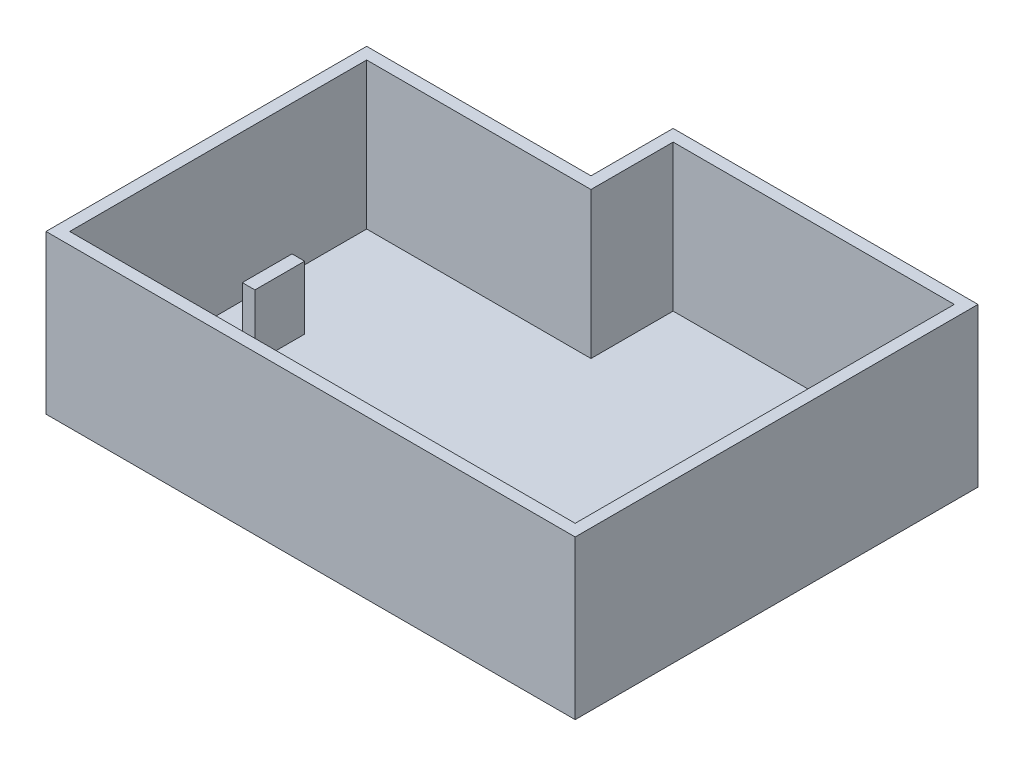
SolidWorks part; units mm, degrees
material "Cedro"
ref_plane "Alzado" through (0, 0, 0) normal (0, 0, 1) x (1, 0, 0)
ref_plane "Planta" through (0, 0, 0) normal (0, 1, 0) x (1, 0, 0)
ref_plane "Vista lateral" through (0, 0, 0) normal (1, 0, 0) x (0, 0, -1)
sketch "Croquis1" plane through (0, 0, 0) normal (0, 1, 0) x (1, 0, 0)
  line L0 (-106.3625, -93.6625) -> (-106.3625, 93.6625)
  line L1 (-101.6, -88.9) -> (101.6, -88.9)
  line L2 (-101.6, -88.9) -> (-101.6, 88.9)
  line L3 (-101.6, 88.9) -> (101.6, 88.9)
  line L4 (101.6, -88.9) -> (101.6, 88.9)
  line L5 (-101.6, -88.9) -> (101.6, 88.9) construction
  line L6 (-101.6, 88.9) -> (101.6, -88.9) construction
  line L7 (-106.3625, 93.6625) -> (106.3625, 93.6625)
  line L8 (106.3625, -93.6625) -> (106.3625, 93.6625)
  line L9 (-106.3625, -93.6625) -> (106.3625, -93.6625)
  point P0 (0, 0)
  dimension "D1" = 203.2
  dimension "D2" = 177.8
  dimension "D3" = 4.7625
extrude "Saliente-Extruir1" add sketch "Croquis1" along normal blind 63.608 contours L1 L4 L3 L2 | L0 L9 L8 L7 L4 L1 L2 L3 region at (-103.528, 0, 0) region at (0, 0, 0)
shell "Vaciado1" thickness 4.7625 removed face at (0, 63.608, 0)
sketch "Croquis2" plane through (0, 4.7625, 0) normal (0, 1, 0) x (1, 0, 0)
  line L0 (-77.47, 10) -> (-77.47, -10)
  line L1 (-101.6, 88.9) -> (101.6, 88.9) construction
  line L3 (10, -64.77) -> (-10, -64.77)
  line L4 (-54.45, 58.42) -> (-34.45, 58.42)
  line L5 (-101.6, -88.9) -> (-101.6, 88.9) construction
  line L6 (-101.6, -88.9) -> (101.6, -88.9) construction
  line L7 (101.6, -88.9) -> (101.6, 88.9) construction
  line L8 (-54.45, 58.42) -> (-54.45, 68.58)
  line L9 (-54.45, 63.5) -> (-34.45, 63.5)
  line L10 (-54.45, 68.58) -> (-34.45, 68.58)
  line L13 (-34.45, 58.42) -> (-34.45, 68.58)
  line L14 (77.47, -18.575) -> (77.47, -38.575)
  line L15 (-54.45, 58.42) -> (-34.45, 68.58) construction
  line L16 (-54.45, 68.58) -> (-34.45, 58.42) construction
  line L17 (72.39, -38.575) -> (82.55, -38.575)
  line L18 (72.39, -38.575) -> (72.39, -18.575)
  line L19 (72.39, -18.575) -> (82.55, -18.575)
  line L20 (82.55, -38.575) -> (82.55, -18.575)
  line L21 (72.39, -38.575) -> (82.55, -18.575) construction
  line L22 (72.39, -18.575) -> (82.55, -38.575) construction
  line L23 (-10, -69.85) -> (10, -69.85)
  line L24 (-10, -69.85) -> (-10, -59.69)
  line L25 (-10, -59.69) -> (10, -59.69)
  line L26 (10, -69.85) -> (10, -59.69)
  line L27 (-10, -69.85) -> (10, -59.69) construction
  line L28 (-10, -59.69) -> (10, -69.85) construction
  line L29 (-72.39, -10) -> (-82.55, -10)
  line L30 (-72.39, -10) -> (-72.39, 10)
  line L31 (-72.39, 10) -> (-82.55, 10)
  line L32 (-82.55, -10) -> (-82.55, 10)
  line L33 (-72.39, -10) -> (-82.55, 10) construction
  line L34 (-72.39, 10) -> (-82.55, -10) construction
  point P1 (-44.45, 63.5)
  point P17 (77.47, -28.575)
  point P23 (0, -64.77)
  point P29 (-77.47, 0)
  dimension "D1" = 24.13
  dimension "D2" = 24.13
  dimension "D3" = 24.13
  dimension "D4" = 25.4
  dimension "D7" = 20
  dimension "D8" = 10.16
extrude "Saliente-Extruir3" add sketch "Croquis2" along normal blind 25.4 contours L9 L13 L10 L8 | L32 L29 L0 L31 | L23 L26 L3 L24 | L17 L20 L19 L14 region at (-80.01, 4.7625, 0) region at (0, 4.7625, 67.31) region at (-44.45, 4.7625, -66.04) region at (80.01, 4.7625, 28.575)
extrude "Saliente-Extruir4" add sketch "Croquis2<5>" along normal blind 6.5 contours L30 L31 L0 L29 | L3 L26 L25 L24 | L19 L18 L17 L14 region at (-74.93, 4.7625, 0) region at (0, 4.7625, 62.23) region at (74.93, 4.7625, 28.575)
sketch "Croquis2<5>" plane through (0, 4.7625, 0) normal (0, 1, 0) x (1, 0, 0) same geometry as "Croquis2"
sketch "Croquis3" plane through (0, 63.608, 0) normal (0, 1, 0) x (1, 0, 0)
  line L0 (11.43, 30.48) -> (106.3625, 30.48)
  line L2 (106.3625, -93.6625) -> (106.3625, 93.6625) construction
  line L3 (11.43, 93.6625) -> (11.43, 30.48)
  line L4 (-106.3625, 93.6625) -> (106.3625, 93.6625) construction
  line L5 (11.43, 93.6625) -> (106.3625, 93.6625)
  line L6 (106.3625, 93.6625) -> (106.3625, 30.48)
  line L7 (-77.47, 10) -> (-77.47, -10) construction
  line L8 (10, -64.77) -> (-10, -64.77) construction
  dimension "D1" = 88.9
  dimension "D2" = 95.25
extrude "Cortar-Extruir1" cut sketch "Croquis3" against normal through all
sketch "Croquis4" plane through (0, 0, 0) normal (0, 1, 0) x (1, 0, 0)
  line L0 (11.43, 93.6625) -> (16.1925, 93.6625)
  line L1 (16.1925, 93.6625) -> (16.1925, 35.2425)
  line L2 (16.1925, 35.2425) -> (106.3625, 35.2425)
  line L3 (106.3625, 35.2425) -> (106.3625, 30.48)
  line L4 (106.3625, 30.48) -> (11.43, 30.48)
  line L5 (11.43, 30.48) -> (11.43, 93.6625)
  dimension "D1" = 4.7625
extrude "Saliente-Extruir5" add sketch "Croquis4" along normal up to surface (63.608 mm away) up to face at (2.286, 63.608, -6.096)
sketch "Croquis5" plane through (0, 0, 0) normal (0, 1, 0) x (1, 0, 0)
  line L0 (16.1925, 35.2425) -> (16.1925, 93.6625) construction
  line L1 (-106.3625, 93.6625) -> (16.1925, 93.6625)
  line L2 (-106.3625, 93.6625) -> (-106.3625, 63.5)
  line L3 (-106.3625, 63.5) -> (16.1925, 63.5)
  line L4 (16.1925, 93.6625) -> (16.1925, 63.5)
  line L5 (-54.45, 63.5) -> (-34.45, 63.5) construction
extrude "Cortar-Extruir2" cut sketch "Croquis5" along normal through all
sketch "Croquis6" plane through (0, 0, 0) normal (0, 1, 0) x (1, 0, 0)
  line L0 (16.1925, 35.2425) -> (16.1925, 63.5) construction
  line L1 (-106.3625, 63.5) -> (16.1925, 63.5)
  line L2 (-106.3625, 63.5) -> (-106.3625, 68.2625)
  line L3 (-106.3625, 68.2625) -> (16.1925, 68.2625)
  line L4 (16.1925, 63.5) -> (16.1925, 68.2625)
  dimension "D1" = 4.7625
extrude "Saliente-Extruir6" add sketch "Croquis6" along normal up to surface (63.608 mm away) up to face at (4.6038, 63.608, -1.6933)
sketch "Croquis7" plane through (0, 63.608, 0) normal (0, 1, 0) x (1, 0, 0)
  line L0 (-77.47, 10) -> (-77.47, -10) construction
  line L1 (-77.47, 17.8902) -> (77.47, 17.8902)
  line L2 (-77.47, 17.8902) -> (-77.47, -64.77)
  line L3 (-77.47, -64.77) -> (77.47, -64.77)
  line L4 (77.47, 17.8902) -> (77.47, -64.77)
  line L5 (77.47, -18.575) -> (77.47, -38.575) construction
  line L6 (10, -64.77) -> (-10, -64.77) construction
extrude "Cortar-Extruir3" cut sketch "Croquis7" against normal up to surface (58.8455 mm away) up to face at (77.47, 4.7625, 28.575)
mirror "Simetría1" about plane through (106.3625, 63.608, 0) normal (-1, 0, 0) of bodies 109
sketch "Croquis8" plane through (0, 0, 93.6625) normal (0, 0, 1) x (1, 0, 0)
  line L1 (-106.3625, 63.608) -> (106.3625, 63.608)
  line L2 (-106.3625, 63.608) -> (-106.3625, 0)
  line L3 (-106.3625, 0) -> (106.3625, 0)
  line L4 (106.3625, 63.608) -> (106.3625, 0)
extrude "Cortar-Extruir4" cut sketch "Croquis8" against normal through all
